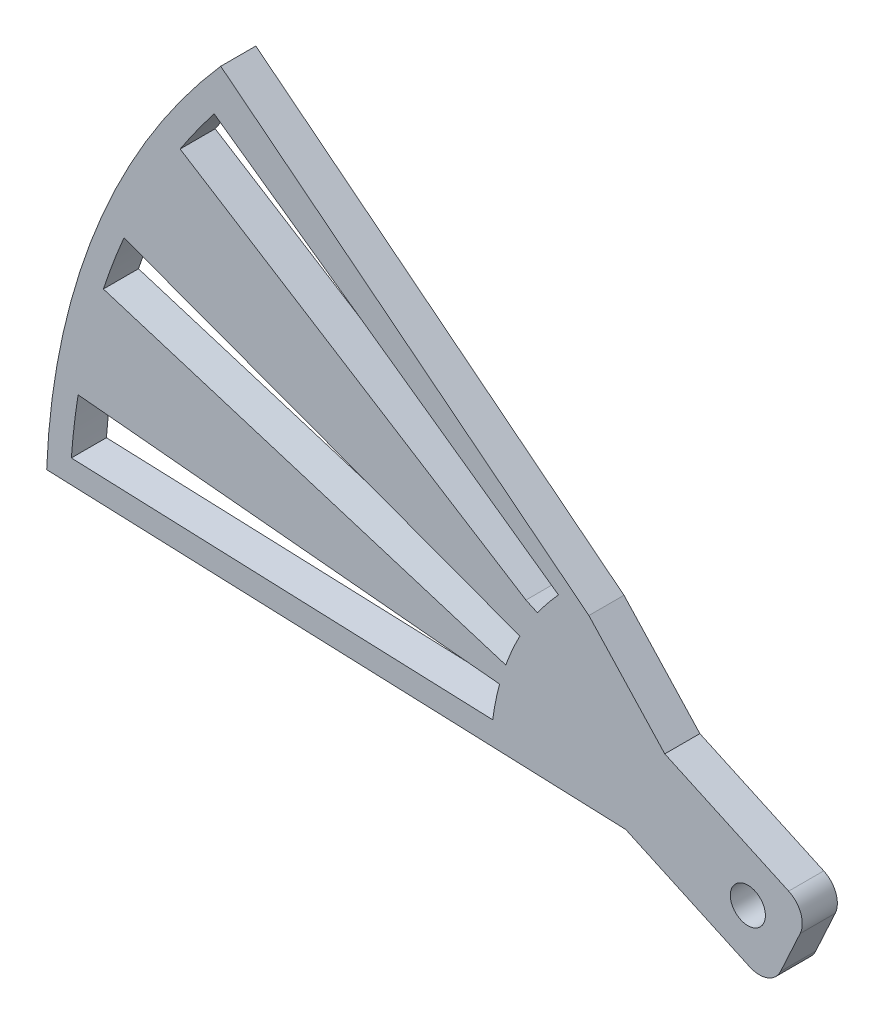
SolidWorks part; units mm, degrees
ref_plane "Front Plane" through (0, 0, 0) normal (0, 0, 1) x (1, 0, 0)
ref_plane "Top Plane" through (0, 0, 0) normal (0, 1, 0) x (1, 0, 0)
ref_plane "Right Plane" through (0, 0, 0) normal (1, 0, 0) x (0, 0, -1)
sketch "Sketch1" plane through (0, 0, 0) normal (0, 0, 1) x (1, 0, 0)
  line L0 (-19.9854, 0.7628) -> (-59.9563, 2.2884)
  line L1 (-16.3569, 14.7123) -> (-16.1915, 14.8941)
  line L2 (0, 0) -> (-50.7795, 31.96) construction
  line L3 (0, 0) -> (-57.3211, 17.7283) construction
  line L4 (-21.8167, 2.8342) -> (-57.8471, 4.2094)
  line L5 (-13.5925, 14.6712) -> (-45.0737, 39.6026)
  line L6 (-21.2283, 5.7759) -> (-57.2696, 9.1759)
  line L7 (-57.0177, 18.6812) -> (-57.0256, 18.6836)
  line L8 (-20.7005, 7.449) -> (-55.1067, 18.0901)
  line L9 (-19.4947, 10.196) -> (-53.3439, 22.7691)
  line L10 (-18.0672, 12.5529) -> (-48.5469, 31.7364)
  line L11 (-50.2398, 32.8019) -> (-50.2468, 32.8063)
  line L12 (0.5327, 0.8463) -> (-50.2468, 32.8063) construction
  line L13 (-16.1915, 14.8941) -> (-45.6332, 35.7997)
  line L15 (-16.3569, 14.7123) -> (-40.8618, 41.162) construction
  line L16 (-13.5925, 14.6712) -> (-40.7774, 44.0137) construction
  line L18 (-54.5167, 25.0585) -> (22.4523, -10.3202) construction
  line L19 (1.9639, -5.305) -> (5.305, 1.9639)
  line L20 (-7.1038, 7.6676) -> (-13.5925, 14.6712)
  line L21 (-18.9747, 13.124) -> (-16.1345, 11.8185)
  line L22 (-7.1038, 7.6676) -> (5.305, 1.9639)
  line L23 (-10.4449, 0.3987) -> (-19.9854, 0.7628)
  line L24 (-10.4449, 0.3987) -> (1.9639, -5.305)
  line L25 (-22.3798, 5.8845) -> (-19.4756, 4.5496)
  arc A0 (-45.0737, 39.6026) -> (-59.9563, 2.2884) centre (0, 0) ccw
  arc A1 (-13.5925, 14.6712) -> (-19.9854, 0.7628) centre (0, 0) ccw
  arc A2 (-45.6332, 35.7997) -> (-48.5469, 31.7364) centre (0, 0) ccw
  arc A3 (-16.3569, 14.7123) -> (-18.0672, 12.5529) centre (0, 0) ccw
  arc A4 (-53.3439, 22.7691) -> (-55.1067, 18.0901) centre (0, 0) ccw
  arc A5 (-40.8618, 41.162) -> (-57.8471, 4.2094) centre (0, 0) ccw construction
  arc A6 (-19.4947, 10.196) -> (-20.7005, 7.449) centre (0, 0) ccw
  arc A7 (-21.2283, 5.7759) -> (-21.8167, 2.8342) centre (0, 0) ccw
  arc A8 (-16.3569, 14.7123) -> (-21.8167, 2.8342) centre (0, 0) ccw construction
  arc A9 (-57.2696, 9.1759) -> (-57.8471, 4.2094) centre (0, 0) ccw
  circle A10 centre (0, 0) radius 1.5
  arc A11 (-40.7774, 44.0137) -> (-59.9563, 2.2884) centre (0, 0) ccw construction
  point P16 (0.2955, 0.9554)
  point P33 (-56.1873, 21.4241)
  point P34 (20.7818, -13.9546)
  point P35 (-52.8461, 28.693)
  point P36 (24.1229, -6.6857)
  dimension "D1" = 120
  dimension "D2" = 40
  dimension "D16" = 3
  dimension "D3" = 0.2459
  dimension "D4" = 15
  dimension "D5" = 2
  dimension "15" = 15
  dimension "D6" = 3
  dimension "D7" = 5
  dimension "D8" = 3
  dimension "D9" = 5
  dimension "D11" = 3
  dimension "D12" = 5
  dimension "D13" = 3
  dimension "D15" = 4
  dimension "D10" = 1
extrude "Boss-Extrude2" add sketch "Sketch1" along normal blind 3 contours L0 A0 L5 A1
extrude "Cut-Extrude1" cut sketch "Sketch1<5>" along normal through all contours A6 L9 A4 L8 | L6 A9 L4 A7 | A3 L1 L13 A2 L10 | L4 A9 L6 A7 | L8 A4 L9 A6 region at (-41.1268, 5.6046, 0) region at (-33.401, 24.6128, 0) region at (-38.6238, 15.1254, 0)
sketch "Sketch1<5>" plane through (0, 0, 0) normal (0, 0, 1) x (1, 0, 0) same geometry as "Sketch1"
extrude "Boss-Extrude5" add sketch "Sketch1<8>" along normal blind 3 contours L20 A1 L23 L24 L19 L22 A10 region at (-8.6534, 3.9775, 0)
sketch "Sketch1<8>" plane through (0, 0, 0) normal (0, 0, 1) x (1, 0, 0) same geometry as "Sketch1"
fillet "Fillet1" radius 2 2 edges at (5.305, 1.9639, 1.5) (1.9639, -5.305, 1.5)
